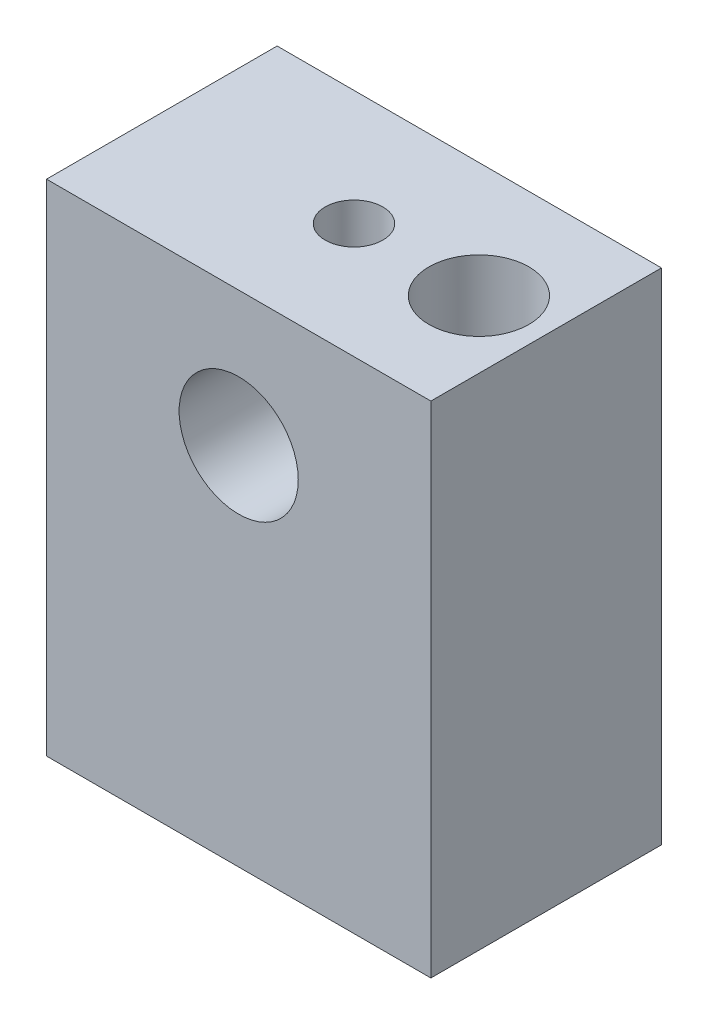
SolidWorks part; units mm, degrees
material "Brass"
ref_plane "Front Plane" through (0, 0, 0) normal (0, 0, 1) x (1, 0, 0)
ref_plane "Top Plane" through (0, 0, 0) normal (0, 1, 0) x (1, 0, 0)
ref_plane "Right Plane" through (0, 0, 0) normal (1, 0, 0) x (0, 0, -1)
sketch "Sketch1" plane through (0, 0, 0) normal (0, 0, 1) x (1, 0, 0)
  line L0 (-10, 0) -> (10, 0)
  line L1 (10, 0) -> (10, 26)
  line L2 (10, 26) -> (-10, 26)
  line L3 (-10, 26) -> (-10, 0)
  dimension "D1" = 20
  dimension "D2" = 26
  dimension "D3" = 10
extrude "Boss-Extrude1" add sketch "Sketch1" along normal blind 12
sketch "Sketch2" plane through (0, 0, 0) normal (0, 0, 1) x (1, 0, 0)
  circle A0 centre (0, 19) radius 3.1
  dimension "D2" = 6.2
  dimension "D1" = 19
extrude "Cut-Extrude1" cut sketch "Sketch2" against normal mid plane 80
sketch "Sketch3" plane through (0, 0, 0) normal (0, 1, 0) x (1, 0, 0)
  circle A0 centre (6.5, -6) radius 2.6
  circle A1 centre (0, -6) radius 1.5
  dimension "D3" = 5.2
  dimension "D5" = 3
  dimension "D1" = 6.5
  dimension "D2" = 6
  dimension "D4" = 6
extrude "Cut-Extrude2" cut sketch "Sketch3" against normal mid plane 80
